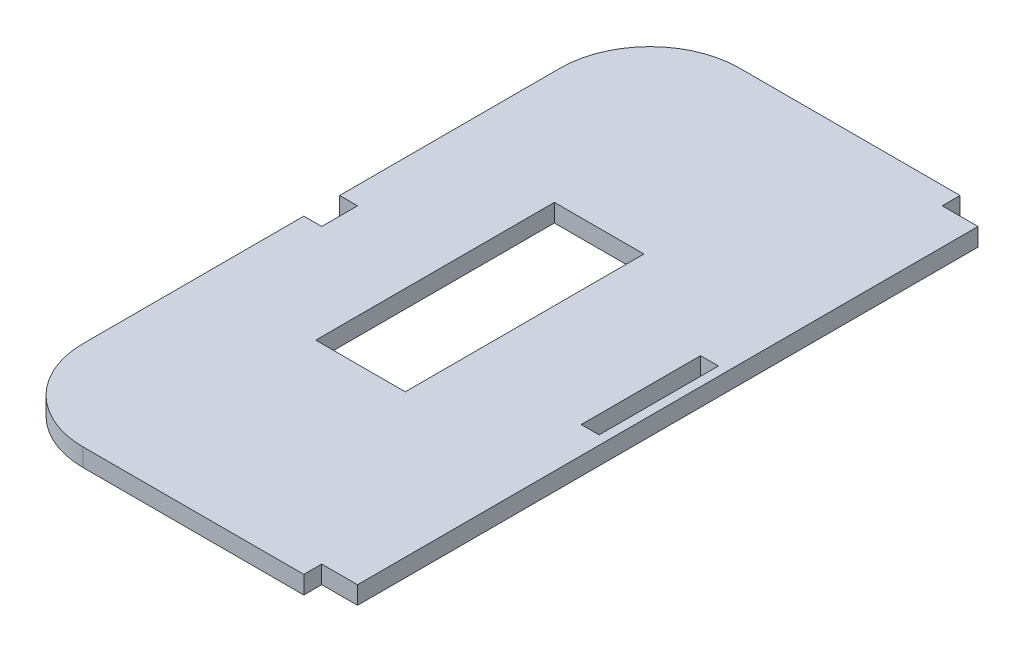
SolidWorks part; units mm, degrees
ref_plane "Спереди" through (0, 0, 0) normal (0, 0, 1) x (1, 0, 0)
ref_plane "Сверху" through (0, 0, 0) normal (0, 1, 0) x (1, 0, 0)
ref_plane "Справа" through (0, 0, 0) normal (1, 0, 0) x (0, 0, -1)
other "Configuration Table"
sketch "Эскиз4" plane through (0, 0, 0) normal (0, 1, 0) x (1, 0, 0)
  line L1 (0, 0) -> (52, 0)
  line L2 (0, 0) -> (0, 52)
  line L3 (0, 110) -> (52, 110)
  line L6 (55, 107) -> (55, 3) construction
  line L7 (52, 107) -> (55, 107)
  line L8 (55, 107) -> (58, 107)
  line L9 (52, 107) -> (52, 110)
  line L12 (55, 3) -> (58, 3)
  line L13 (55, 3) -> (52, 3)
  line L14 (52, 3) -> (52, 0)
  line L15 (3, 55) -> (3, 58)
  line L16 (3, 55) -> (3, 52)
  line L17 (3, 58) -> (0, 58)
  line L18 (3, 52) -> (0, 52)
  line L19 (0, 58) -> (0, 110)
  line L21 (58, 107) -> (58, 3)
  dimension "D1" = 110
  dimension "D2" = 55
  dimension "D3" = 3
  dimension "D4" = 3
  dimension "D5" = 3
  dimension "D6" = 3
  dimension "D7" = 3
  dimension "D8" = 3
  dimension "D9" = 3
extrude "Бобышка-Вытянуть3" add sketch "Эскиз4" along normal blind 3 contours L3 L8 L9 L2 L17 L15 L16 L18 L1 L14 L13 L12 | L7 L8 L21 L12 L13 L14 L1 L2 L18 L16 L15 L17 L19 L3 L9 region at (28.9303, 0, -55)
sketch "Sketch1" plane through (0, 3, 0) normal (0, 1, 0) x (1, 0, 0)
  line L0 (3, 52) -> (3, 58) construction
  line L13 (3, 55) -> (107, 55) construction
  line L15 (55, 107) -> (55, 3) construction
  line L16 (52, 107) -> (58, 107) construction
  line L17 (58, 3) -> (52, 3) construction
  line L19 (19, 75) -> (34, 75)
  line L20 (19, 75) -> (19, 35)
  line L21 (19, 35) -> (34, 35)
  line L22 (34, 75) -> (34, 35)
  line L23 (53.5, 65) -> (56.5, 65)
  line L24 (53.5, 65) -> (53.5, 45)
  line L25 (53.5, 45) -> (56.5, 45)
  line L26 (56.5, 65) -> (56.5, 45)
  dimension "D1" = 3
  dimension "D2" = 20
  dimension "D3" = 16
  dimension "D4" = 15
  dimension "D5" = 40
extrude "Cut-Extrude1" cut sketch "Sketch1" against normal blind 10
fillet "Fillet1" radius 15 2 edges at (0, 1.5, 0) (0, 1.5, -110)
